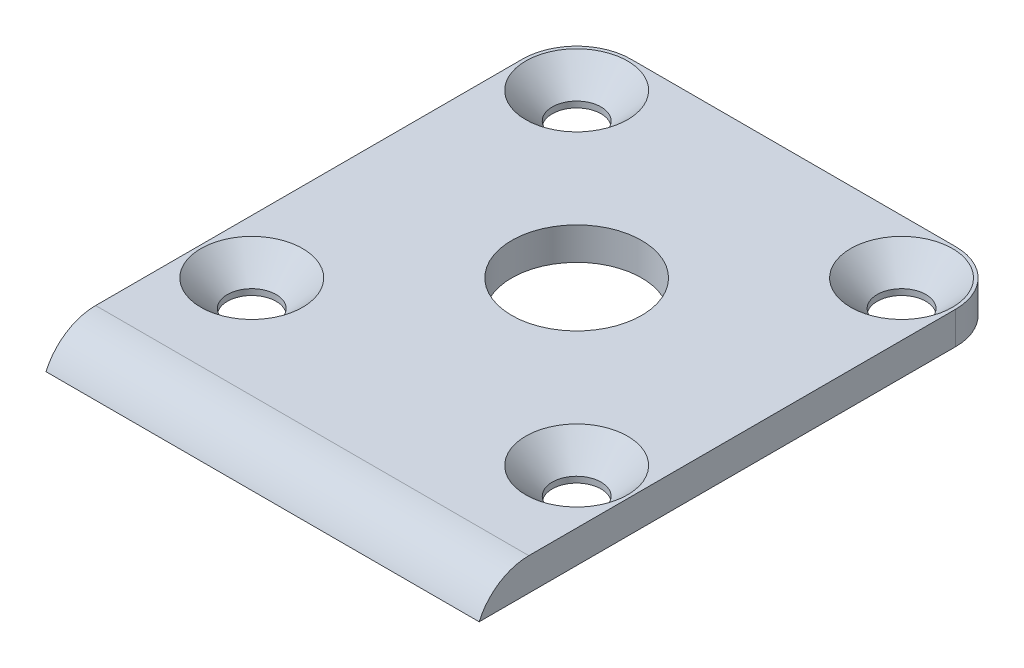
SolidWorks part; units mm, degrees
ref_plane "Front Plane" through (0, 0, 0) normal (0, 0, 1) x (1, 0, 0)
ref_plane "Top Plane" through (0, 0, 0) normal (0, 1, 0) x (1, 0, 0)
ref_plane "Right Plane" through (0, 0, 0) normal (1, 0, 0) x (0, 0, -1)
sketch "Sketch1" plane through (0, 0, 0) normal (0, 1, 0) x (1, 0, 0)
  line L0 (20, 49) -> (20, 0) construction
  line L1 (0, 0) -> (40, 0)
  line L2 (0, 0) -> (0, 49)
  line L3 (0, 49) -> (40, 49)
  line L4 (40, 0) -> (40, 49)
  line L6 (5, 14) -> (35, 14)
  line L7 (5, 14) -> (5, 44)
  line L8 (5, 44) -> (35, 44)
  line L9 (35, 14) -> (35, 44)
  line L10 (5, 14) -> (35, 44) construction
  line L11 (5, 44) -> (35, 14) construction
  point P7 (20, 29)
  dimension "D1" = 40
  dimension "D2" = 49
  dimension "D3" = 5
  dimension "D4" = 5
extrude "Boss-Extrude1" add sketch "Sketch1" along normal blind 3 contours L6 L9 L8 L7 | L1 L4 L3 L2 L9 L6 L7 L8 region at (0.6325, 0, -24.5) region at (20, 0, -29)
fillet "Fillet1" radius 5 3 edges at (20, 3, 0) (0, 1.5, -49) (40, 1.5, -49)
hole_wizard "CSK for M4 Flat Head Machine Screw2" positions "Sketch2" profile "Sketch3" countersink size "M4" standard "ANSI Metric" end condition through all
sketch "Sketch2" plane through (0, 3, 0) normal (0, 1, 0) x (1, 0, 0)
  point P0 (5, 44)
  point P3 (35, 44)
  point P6 (35, 14)
  point P9 (5, 14)
sketch "Sketch3" plane through (5, 3, -44) normal (1, 0, 0) x (0, 0, 1)
  line L0 (0, 0) -> (0, 3)
  line L1 (0, 3) -> (2.25, 3)
  line L2 (2.25, 3) -> (2.25, 2.45)
  line L3 (2.25, 2.45) -> (4.7, 0)
  line L5 (4.7, 0) -> (0, 0)
  line L6 (-2.25, 2.45) -> (-4.7, 0) construction
  line L11 (0, -6.35) -> (0, 107.95) construction
  dimension "Thru Hole Dia." = 4.5
  dimension "Thru Hole Depth" = 3
  dimension "Near C'Sink Dia." = 9.4
  dimension "Near C'Sink Angle" = 90
sketch "Sketch4" plane through (0, 3, 0) normal (0, 1, 0) x (1, 0, 0)
  circle A0 centre (20, 29) radius 6
  dimension "D1" = 12
extrude "Cut-Extrude1" cut sketch "Sketch4" against normal blind 3
